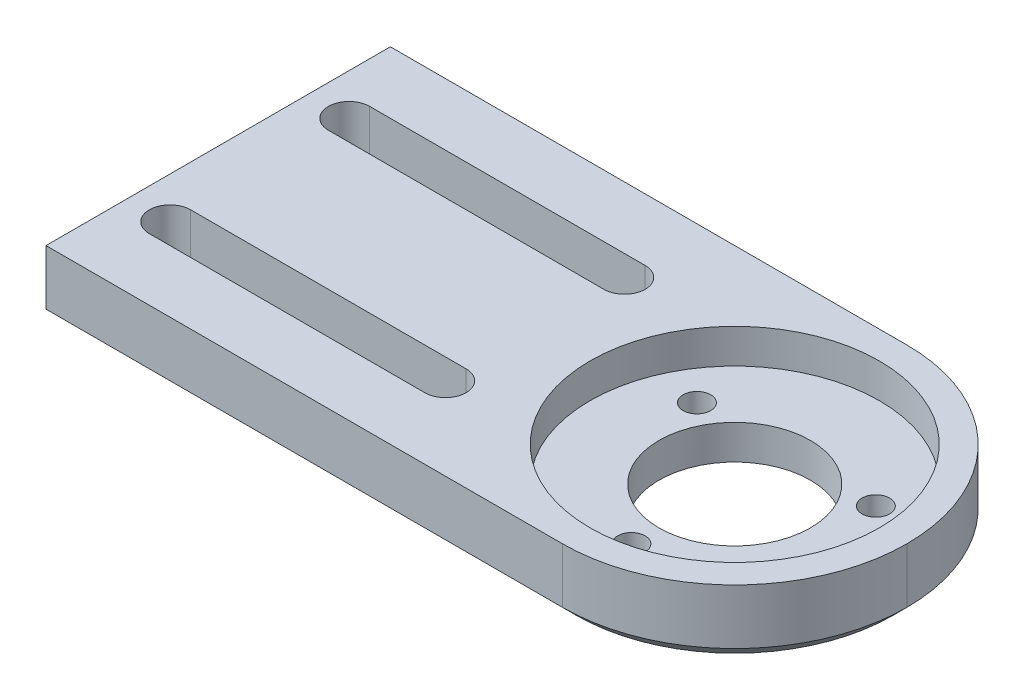
SolidWorks part; units mm, degrees
ref_plane "Płaszczyzna przednia" through (0, 0, 0) normal (0, 0, 1) x (1, 0, 0)
ref_plane "Płaszczyzna górna" through (0, 0, 0) normal (0, 1, 0) x (1, 0, 0)
ref_plane "Płaszczyzna prawa" through (0, 0, 0) normal (1, 0, 0) x (0, 0, -1)
sketch "Sketch1" plane through (0, 0, 0) normal (0, 1, 0) x (1, 0, 0)
  line L1 (0, 0) -> (100, 0)
  line L2 (0, 0) -> (0, 50)
  line L3 (0, 50) -> (100, 50)
  line L4 (100, 0) -> (100, 50)
  dimension "D1" = 100
  dimension "D2" = 50
extrude "Boss-Extrude1" add sketch "Sketch1" along normal blind 10
fillet "Fillet1" radius 25 2 edges at (100, 5, -50) (100, 5, 0)
sketch "Sketch2" plane through (0, 0, 0) normal (0, 1, 0) x (1, 0, 0)
  circle A0 centre (75, 25) radius 11
  circle A1 centre (75, 25) radius 15 construction
  circle A2 centre (75, 10) radius 2
  circle A3 centre (62.0096, 32.5) radius 2
  circle A4 centre (87.9904, 32.5) radius 2
  point P6 (0, 0)
  point P7 (0, 0)
  point P13 (75, 25)
  dimension "D1" = 22
  dimension "D2" = 30
  dimension "D3" = 4
  dimension "D4" = 3
extrude "Cut-Extrude1" cut sketch "Sketch2" along normal through all both and the other way through all
sketch "Sketch3" plane through (0, 10, 0) normal (0, 1, 0) x (1, 0, 0)
  circle A0 centre (75, 25) radius 21
  dimension "D1" = 42
extrude "Cut-Extrude2" cut sketch "Sketch3" against normal blind 5
sketch "Sketch4" plane through (0, 0, 0) normal (0, 1, 0) x (1, 0, 0)
  line L0 (6, 12) -> (46, 12) construction
  line L1 (6, 15) -> (46, 15)
  line L2 (6, 9) -> (46, 9)
  line L3 (46, 38) -> (6, 38) construction
  line L4 (46, 35) -> (6, 35)
  line L5 (46, 41) -> (6, 41)
  line L7 (0, 50) -> (0, 0) construction
  line L8 (0, 0) -> (75, 0) construction
  line L9 (75, 50) -> (0, 50) construction
  arc A0 (6, 15) -> (6, 9) centre (6, 12) ccw
  arc A1 (46, 9) -> (46, 15) centre (46, 12) ccw
  arc A2 (46, 35) -> (46, 41) centre (46, 38) ccw
  arc A3 (6, 41) -> (6, 35) centre (6, 38) ccw
  point P2 (26, 12)
  point P8 (26, 38)
  point P14 (29.2888, 36.0106)
  dimension "D1" = 6
  dimension "D2" = 6
  dimension "D3" = 6
  dimension "D4" = 12
  dimension "D5" = 12
  dimension "D6" = 40
extrude "Cut-Extrude3" cut sketch "Sketch4" along normal through all both and the other way through all
chamfer "Chamfer1" distance 2 angle 45 5 edges at (37.5, 0, 0) (92.6777, 0, -7.3223) (92.6777, 0, -42.6777) (0, 0, -25) (37.5, 0, -50)
